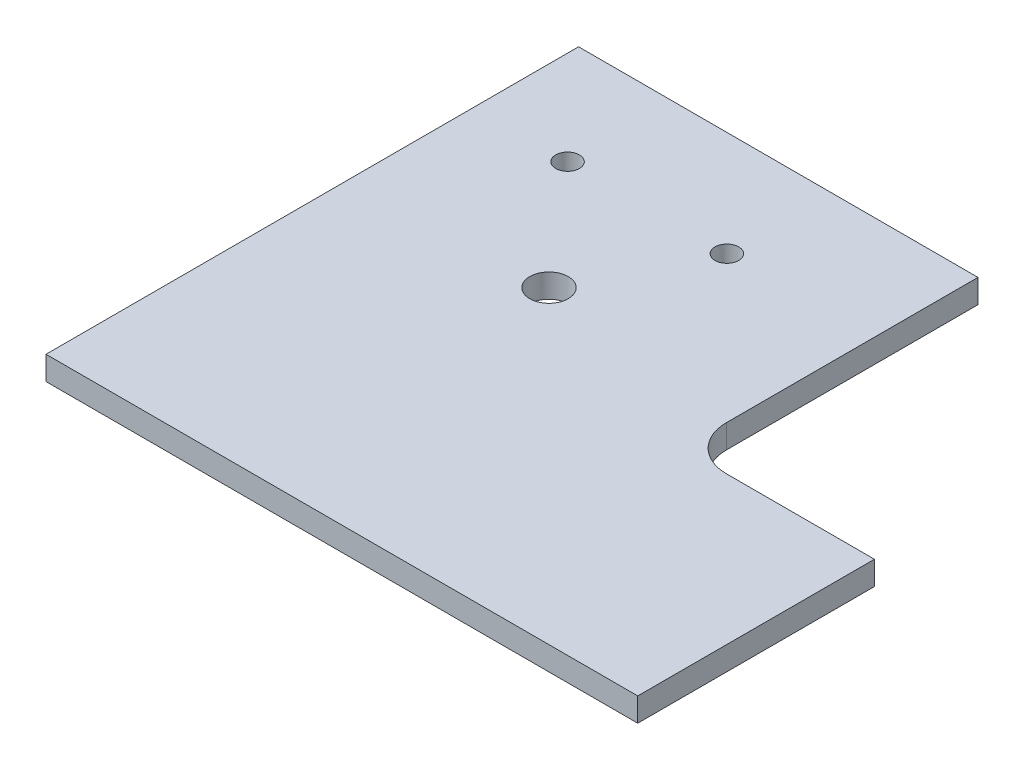
SolidWorks part; units mm, degrees
ref_plane "Front Plane" through (0, 0, 0) normal (0, 0, 1) x (1, 0, 0)
ref_plane "Top Plane" through (0, 0, 0) normal (0, 1, 0) x (1, 0, 0)
ref_plane "Right Plane" through (0, 0, 0) normal (1, 0, 0) x (0, 0, -1)
sketch "Sketch1" plane through (0, 0, 0) normal (0, 1, 0) x (1, 0, 0)
  line L2 (-13.5, -10) -> (-13.5, 10)
  line L3 (-13.5, 10) -> (13.5, 10)
  line L4 (13.5, -10) -> (13.5, 10)
  line L5 (-13.5, -10) -> (13.5, 10) construction
  line L6 (-13.5, 10) -> (13.5, -10) construction
  line L7 (26.5, -26) -> (-13.5, -26)
  line L8 (26.5, -26) -> (26.5, -10)
  line L9 (26.5, -10) -> (13.5, -10)
  line L10 (-13.5, -26) -> (-13.5, -10)
  line L11 (26.5, -26) -> (-13.5, -10) construction
  line L12 (26.5, -10) -> (-13.5, -26) construction
  point P0 (0, 0)
  point P6 (6.5, -18)
  point P11 (6.5, -18)
  dimension "D1" = 27
  dimension "D2" = 20
  dimension "D7" = 40
  dimension "D8" = 16
extrude "Boss-Extrude1" add sketch "Sketch1" along normal blind 1.6
fillet "Fillet1" radius 3 1 edges at (13.5, 0.8, 10)
hole_wizard "M2 Clearance Hole1" positions "Sketch2" profile "Sketch3" hole size "M2" standard "ANSI Metric" end condition through all
sketch "Sketch2" plane through (0, 1.6, 0) normal (0, 1, 0) x (1, 0, 0)
  line L0 (-13.5, 10) -> (-13.5, -26) construction
  line L1 (13.5, 10) -> (-13.5, 10) construction
  point P0 (-0.4, -5.1)
  dimension "D1" = 13.1
  dimension "D2" = 15.1
sketch "Sketch3" plane through (-0.4, 1.6, 5.1) normal (1, 0, 0) x (0, 0, 1)
  line L0 (0, 0) -> (0, 1.6)
  line L1 (0, 1.6) -> (1.3, 1.6)
  line L2 (1.3, 1.6) -> (1.3, 0)
  line L5 (1.3, 0) -> (0, 0)
  line L11 (0, -6.35) -> (0, 107.95) construction
  dimension "Thru Hole Dia." = 2.6
  dimension "Thru Hole Depth" = 1.6
sketch "Sketch5" plane through (0, 1.6, 0) normal (0, 1, 0) x (1, 0, 0)
  line L0 (-7.145, 2.9) -> (3.625, 2.9) construction
  line L5 (-13.5, 10) -> (-13.5, -26) construction
  line L9 (13.5, 10) -> (-13.5, 10) construction
  circle A3 centre (-7.145, 2.9) radius 0.8
  circle A5 centre (3.625, 2.9) radius 0.8
  point P0 (0, 0)
  point P5 (-1.76, 2.9)
  dimension "D1" = 7.1
  dimension "D3" = 11.74
  dimension "D5" = 1.6
  dimension "D2" = 10.77
extrude "Cut-Extrude1" cut sketch "Sketch5" against normal through all both and the other way through all
sketch "Sketch6" plane through (0, 0, 0) normal (0, -1, 0) x (1, 0, 0)
  circle A0 centre (-0.4, 5.1) radius 3
  circle A1 centre (-0.4, 5.1) radius 1.3 construction
  dimension "D1" = 6
extrude "Cut-Extrude2" cut sketch "Sketch6" against normal blind 0.001
